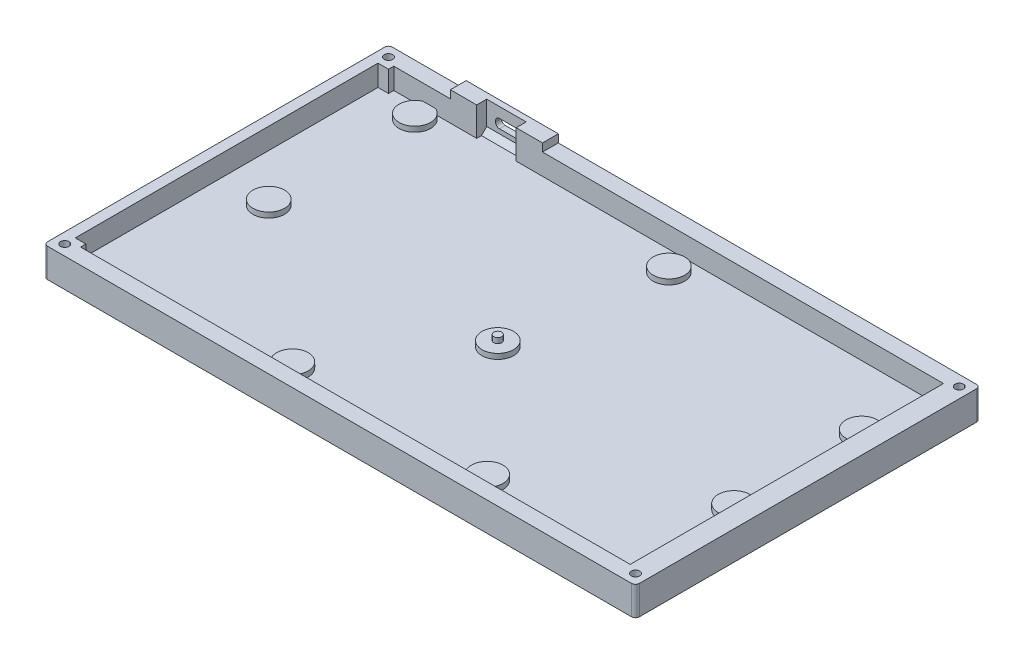
SolidWorks part; units mm, degrees
ref_plane "Front Plane" through (0, 0, 0) normal (0, 0, 1) x (1, 0, 0)
ref_plane "Top Plane" through (0, 0, 0) normal (0, 1, 0) x (1, 0, 0)
ref_plane "Right Plane" through (0, 0, 0) normal (1, 0, 0) x (0, 0, -1)
sketch "Sketch1" plane through (0, 0, 0) normal (0, 1, 0) x (1, 0, 0)
  line L1 (5.9066, 22.7059) -> (230.7145, 22.7059)
  line L2 (5.9066, 22.7059) -> (5.9066, 153.7054)
  line L3 (5.9066, 153.7054) -> (230.7145, 153.7054)
  line L4 (230.7145, 22.7059) -> (230.7145, 153.7054)
  line L6 (35.4018, 153.7054) -> (7.4066, 153.7054) construction
  line L7 (230.7145, 24.2059) -> (230.7145, 152.2054) construction
  line L8 (7.4066, 22.7059) -> (229.2145, 22.7059) construction
  line L9 (5.9066, 152.2054) -> (5.9066, 24.2059) construction
extrude "Boss-Extrude1" add sketch "Sketch1" along normal blind 3
sketch "Sketch2" plane through (0, 3, 0) normal (0, 1, 0) x (1, 0, 0)
  line L9 (5.9066, 22.7059) -> (13.9066, 22.7059)
  line L10 (5.9066, 22.7059) -> (5.9066, 30.7059)
  line L11 (5.9066, 30.7059) -> (13.9066, 30.7059)
  line L12 (13.9066, 22.7059) -> (13.9066, 30.7059)
  line L13 (230.7145, 22.7059) -> (222.7145, 22.7059)
  line L14 (230.7145, 22.7059) -> (230.7145, 30.7059)
  line L15 (230.7145, 30.7059) -> (222.7145, 30.7059)
  line L16 (222.7145, 22.7059) -> (222.7145, 30.7059)
  line L17 (230.7145, 153.7054) -> (222.7145, 153.7054)
  line L18 (230.7145, 153.7054) -> (230.7145, 145.7054)
  line L19 (230.7145, 145.7054) -> (222.7145, 145.7054)
  line L20 (222.7145, 153.7054) -> (222.7145, 145.7054)
  line L21 (5.9066, 153.7054) -> (13.9066, 153.7054)
  line L22 (5.9066, 153.7054) -> (5.9066, 145.7054)
  line L23 (5.9066, 145.7054) -> (13.9066, 145.7054)
  line L24 (13.9066, 153.7054) -> (13.9066, 145.7054)
  dimension "D1" = 8
extrude "Boss-Extrude2" add sketch "Sketch2" along normal blind 8
sketch "Sketch11" plane through (0, 3, 0) normal (0, 1, 0) x (1, 0, 0)
  line L0 (13.9066, 30.7059) -> (5.9066, 30.7059) construction
  line L1 (5.9066, 145.7054) -> (9.9066, 145.7054)
  line L2 (5.9066, 145.7054) -> (5.9066, 30.7059)
  line L3 (5.9066, 30.7059) -> (9.9066, 30.7059)
  line L4 (9.9066, 145.7054) -> (9.9066, 30.7059)
  line L5 (222.7145, 30.7059) -> (222.7145, 22.7059) construction
  line L6 (13.9066, 22.7059) -> (222.7145, 22.7059)
  line L7 (13.9066, 22.7059) -> (13.9066, 28.7059)
  line L8 (13.9066, 28.7059) -> (222.7145, 28.7059)
  line L9 (222.7145, 22.7059) -> (222.7145, 28.7059)
  line L10 (222.7145, 145.7054) -> (230.7145, 145.7054) construction
  line L11 (230.7145, 30.7059) -> (222.7145, 30.7059)
  line L12 (230.7145, 30.7059) -> (230.7145, 145.7054)
  line L13 (230.7145, 145.7054) -> (222.7145, 145.7054)
  line L14 (222.7145, 30.7059) -> (222.7145, 145.7054)
  line L15 (13.9066, 145.7054) -> (13.9066, 153.7054) construction
  line L16 (222.7145, 153.7054) -> (13.9066, 153.7054)
  line L17 (222.7145, 153.7054) -> (222.7145, 147.7054)
  line L18 (222.7145, 147.7054) -> (60.4018, 147.7054)
  line L19 (13.9066, 153.7054) -> (13.9066, 147.7054)
  line L20 (45.4018, 147.7054) -> (13.9066, 147.7054)
  line L22 (60.4018, 147.7054) -> (60.4018, 151.5054)
  line L23 (60.4018, 151.5054) -> (45.4018, 151.5054)
  line L24 (45.4018, 147.7054) -> (45.4018, 151.5054)
  line L30 (5.9066, 153.7054) -> (5.9066, 145.7054) construction
  dimension "D1" = 8
  dimension "D2" = 6
  dimension "D3" = 6
  dimension "D4" = 4
  dimension "D5" = 3.8
  dimension "D6" = 39.4952
  dimension "D7" = 15
extrude "Boss-Extrude4" add sketch "Sketch11" along normal up to surface (8 mm away) up to face at (226.7145, 11, -26.7059)
hole_wizard "CSK for M3 SFHCS1" positions "Sketch5" profile "Sketch6" countersink size "M3" standard "ANSI Metric" end condition through all
sketch "Sketch5" plane through (0, 0, 0) normal (0, -1, 0) x (-1, 0, 0)
  point P29 (-9.9066, 26.7059)
  point P32 (-226.7145, 26.7059)
  point P35 (-226.7145, 149.7054)
  point P38 (-9.9066, 149.7054)
sketch "Sketch6" plane through (9.9066, 0, -26.7059) normal (1, 0, 0) x (0, 0, -1)
  line L0 (0, 0) -> (0, 11)
  line L1 (0, 11) -> (1.6, 11)
  line L2 (1.6, 11) -> (1.6, 1.76)
  line L3 (1.6, 1.76) -> (3.36, 0)
  line L5 (3.36, 0) -> (0, 0)
  line L6 (-1.6, 1.76) -> (-3.36, 0) construction
  line L11 (0, -6.35) -> (0, 107.95) construction
  dimension "Thru Hole Dia." = 3.2
  dimension "Thru Hole Depth" = 11
  dimension "Near C'Sink Dia." = 6.72
  dimension "Near C'Sink Angle" = 90
fillet "Fillet1" radius 1.5 4 edges at (5.9066, 5.5, -153.7054) (5.9066, 5.5, -22.7059) (230.7145, 5.5, -153.7054) (230.7145, 5.5, -22.7059)
sketch "Sketch12" plane through (0, 3, 0) normal (0, 1, 0) x (1, 0, 0)
  circle A0 centre (27.4066, 142.2059) radius 6
  circle A1 centre (27.9066, 86.2059) radius 6
  circle A2 centre (85.9066, 37.2059) radius 6
  circle A3 centre (159.9066, 37.2059) radius 6
  circle A4 centre (216.4066, 74.4559) radius 6
  circle A5 centre (216.1566, 123.2059) radius 6
  circle A6 centre (125.9066, 140.2059) radius 6
  circle A7 centre (117.9066, 83.2059) radius 6
  dimension "D1" = 12
extrude "Boss-Extrude5" add sketch "Sketch12" along normal blind 2
sketch "Sketch13" plane through (0, 5, 0) normal (0, 1, 0) x (1, 0, 0)
  circle A0 centre (117.9066, 83.2059) radius 1.5
  dimension "D1" = 3
extrude "Boss-Extrude6" add sketch "Sketch13" along normal blind 2
sketch "Sketch14" plane through (0, 0, -151.5054) normal (0, 0, 1) x (1, 0, 0)
  line L5 (57.8457, 6.7796) -> (48.8752, 6.7796) construction
  line L6 (57.8457, 6.7796) -> (57.8457, 9.9701) construction
  line L7 (57.8457, 9.9701) -> (48.8752, 9.9701) construction
  line L8 (48.8752, 6.7796) -> (48.8752, 9.9701) construction
  line L9 (50.2752, 6.6796) -> (56.4457, 6.6796)
  line L10 (48.7752, 8.1796) -> (48.7752, 8.5701)
  line L11 (50.2752, 10.0701) -> (56.4457, 10.0701)
  line L12 (57.9457, 8.1796) -> (57.9457, 8.5701)
  arc A4 (48.7752, 8.5701) -> (50.2752, 10.0701) centre (50.2752, 8.5701) cw
  arc A5 (50.2752, 6.6796) -> (48.7752, 8.1796) centre (50.2752, 8.1796) cw
  arc A6 (56.4457, 6.6796) -> (57.9457, 8.1796) centre (56.4457, 8.1796) ccw
  arc A7 (56.4457, 10.0701) -> (57.9457, 8.5701) centre (56.4457, 8.5701) cw
  dimension "D1" = 0.1
  dimension "D5" = 1.5
  dimension "D2" = 0.1
  dimension "D3" = 0.1
  dimension "D4" = 0.1
extrude "Cut-Extrude1" cut sketch "Sketch14" against normal blind 10
sketch "Sketch15" plane through (0, 11, 0) normal (0, 1, 0) x (1, 0, 0)
  line L0 (35.4018, 147.7054) -> (35.4018, 153.7054)
  line L1 (13.9066, 147.7054) -> (45.4018, 147.7054) construction
  line L2 (229.2145, 153.7054) -> (7.4066, 153.7054) construction
  line L3 (35.4018, 153.7054) -> (70.4018, 153.7054)
  line L4 (70.4018, 153.7054) -> (70.4018, 147.7054)
  line L5 (60.4018, 147.7054) -> (222.7145, 147.7054) construction
  line L6 (70.4018, 147.7054) -> (60.4018, 147.7054)
  line L7 (60.4018, 147.7054) -> (60.4018, 151.5054)
  line L8 (60.4018, 151.5054) -> (45.4018, 151.5054)
  line L9 (45.4018, 151.5054) -> (45.4018, 147.7054)
  line L10 (45.4018, 147.7054) -> (35.4018, 147.7054)
  dimension "D1" = 10
  dimension "D2" = 10
extrude "Boss-Extrude7" add sketch "Sketch15" along normal blind 3
chamfer "Chamfer1" distance 2 angle 45 1 edges at (52.9018, 3, -151.5054)
